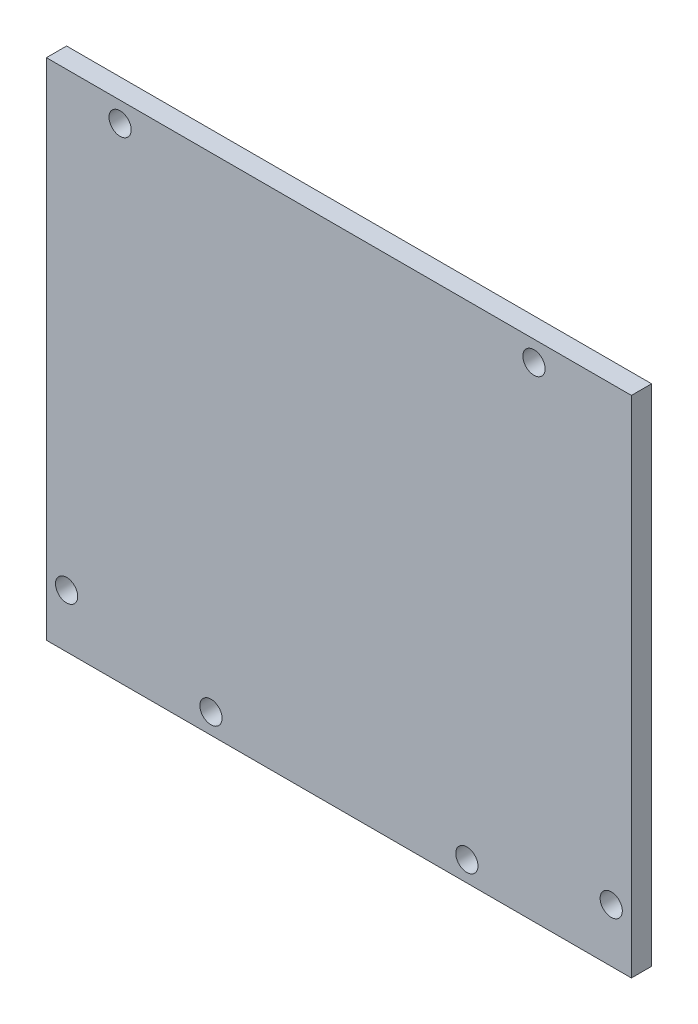
SolidWorks part; units mm, degrees
material "6061-T6 (SS)"
ref_plane "前视基准面" through (0, 0, 0) normal (0, 0, 1) x (1, 0, 0)
ref_plane "上视基准面" through (0, 0, 0) normal (0, 1, 0) x (1, 0, 0)
ref_plane "右视基准面" through (0, 0, 0) normal (1, 0, 0) x (0, 0, -1)
other "Configuration Table"
sketch "草图1" plane through (0, 0, 0) normal (0, 0, 1) x (1, 0, 0)
  line L1 (-4.3, -4.3) -> (53.65, -4.3)
  line L2 (-4.3, -4.3) -> (-4.3, 45.68)
  line L3 (-4.3, 45.68) -> (53.65, 45.68)
  line L4 (53.65, -4.3) -> (53.65, 45.68)
  dimension "D1" = 53.65
  dimension "D2" = 4.3
  dimension "D3" = 45.68
  dimension "D4" = 4.3
extrude "Main_Stock" add sketch "草图1" along normal blind 2 from offset 11.1
sketch "草图2" plane through (0, 0, 13.1) normal (0, 0, 1) x (1, 0, 0)
  circle A0 centre (-2.3, 1) radius 1.1
  circle A1 centre (51.65, 1) radius 1.1
  circle A2 centre (12, -2.3) radius 1.1
  circle A3 centre (37.35, -2.3) radius 1.1
  circle A4 centre (3, 43.68) radius 1.1
  circle A5 centre (44, 43.68) radius 1.1
  dimension "D1" = 2.2
  dimension "D2" = 3
  dimension "D3" = 12
  dimension "D4" = 37.35
  dimension "D5" = 44
  dimension "D6" = 51.65
  dimension "D7" = 2.3
  dimension "D8" = 1
  dimension "D9" = 43.68
  dimension "D10" = 2.3
extrude "Cover_6xD2p2_Through" cut sketch "草图2" against normal through all
